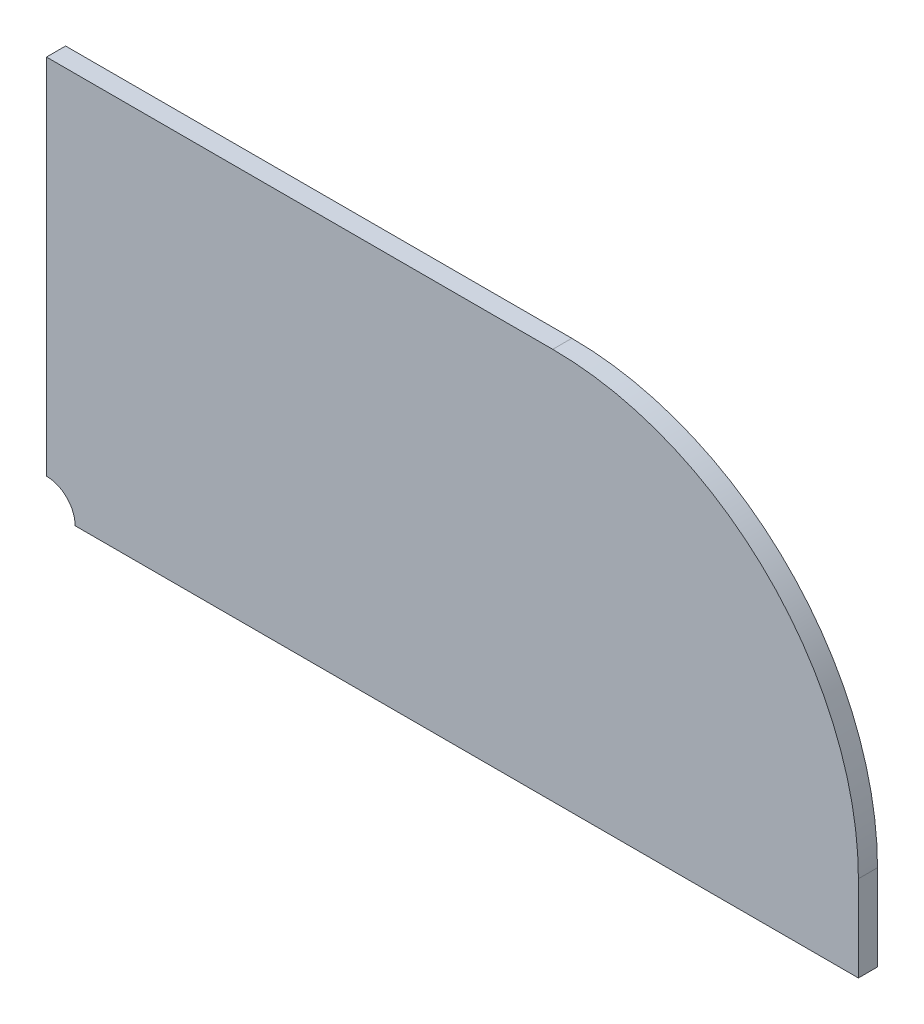
SolidWorks part; units mm, degrees
ref_plane "Front Plane" through (0, 0, 0) normal (0, 0, 1) x (1, 0, 0)
ref_plane "Top Plane" through (0, 0, 0) normal (0, 1, 0) x (1, 0, 0)
ref_plane "Right Plane" through (0, 0, 0) normal (1, 0, 0) x (0, 0, -1)
sketch "Sketch1" plane through (0, 0, 0) normal (0, 0, 1) x (1, 0, 0)
  line L0 (42.5, 4.5) -> (42.5, 0)
  line L1 (42.5, 0) -> (1.5, 0)
  line L2 (0, 1.5) -> (0, 20.5)
  line L3 (0, 20.5) -> (26.5, 20.5)
  arc A0 (42.5, 4.5) -> (26.5, 20.5) centre (26.5, 4.5) ccw
  arc A1 (1.5, 0) -> (0, 1.5) centre (0, 0) ccw
  dimension "D1" = 16
  dimension "D4" = 1.5
  dimension "D2" = 42.5
  dimension "D3" = 4.5
base flange "Base-Flange1" sketch "Sketch1" thickness 1 reverse thickness direction no parameters "D1"=1
sketch "Bend-Lines1" [suppressed] plane through (0, 0, 0) normal (0, 1, 0) x (1, 0, 0)
sketch "Bounding-Box1" [suppressed] plane through (0, 0, 0) normal (0, 1, 0) x (1, 0, 0)
sheet metal parameters "Sheet-Metal1" thickness 1 parameters "D1"=1
flat pattern "Flat-Pattern1" [suppressed]
sketch "Bend-Lines2" plane through (0, 0, 0) normal (0, 1, 0) x (1, 0, 0)
sketch3d "Bounding-Box2" [suppressed]
  line L0 (-26.5, -4.5, 0) -> (16, -4.5, 0) construction
  line L1 (-26.5, 16, 0) -> (16, 16, 0) construction
  line L2 (-26.5, -4.5, 0) -> (-26.5, 16, 0) construction
  line L3 (16, -4.5, 0) -> (16, 16, 0) construction
